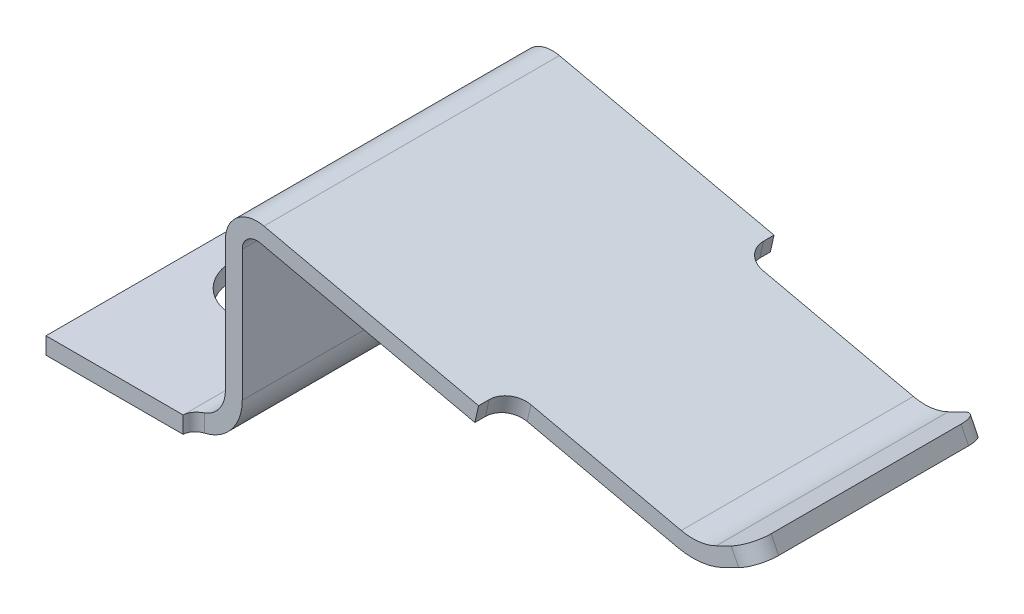
SolidWorks part; units mm, degrees
ref_plane "Спереди" through (0, 0, 0) normal (0, 0, 1) x (1, 0, 0)
ref_plane "Сверху" through (0, 0, 0) normal (0, 1, 0) x (1, 0, 0)
ref_plane "Справа" through (0, 0, 0) normal (1, 0, 0) x (0, 0, -1)
sketch "Эскиз1" plane through (0, 0, 0) normal (0, 0, 1) x (1, 0, 0)
  line L0 (-25.2291, 2.3594) -> (-25.2291, 8.5594)
  line L1 (-33.2291, 0.0594) -> (-26.7291, 0.0594)
  line L2 (-33.2291, 0.0594) -> (-33.2291, 0.8594)
  line L3 (-33.2291, 0.8594) -> (-26.7291, 0.8594)
  line L4 (-24.4291, 2.3594) -> (-24.4291, 8.5594)
  line L5 (-23.4005, 10.023) -> (-5.1266, 5.9201)
  line L6 (-23.5757, 9.2424) -> (-5.3019, 5.1396)
  line L7 (-3.4669, 6.1203) -> (-1.8665, 6.9152)
  line L8 (-3.1111, 5.4038) -> (-1.5106, 6.1987)
  line L9 (-1.8665, 6.9152) -> (-1.5106, 6.1987)
  arc A0 (-5.1266, 5.9201) -> (-3.4669, 6.1203) centre (-4.5789, 8.3594) ccw
  arc A1 (-25.2291, 8.5594) -> (-23.4005, 10.023) centre (-23.7291, 8.5594) cw
  arc A2 (-26.7291, 0.8594) -> (-25.2291, 2.3594) centre (-26.7291, 2.3594) ccw
  arc A3 (-26.7291, 0.0594) -> (-24.4291, 2.3594) centre (-26.7291, 2.3594) ccw
  arc A4 (-24.4291, 8.5594) -> (-23.5757, 9.2424) centre (-23.7291, 8.5594) cw
  arc A5 (-5.3019, 5.1396) -> (-3.1111, 5.4038) centre (-4.5789, 8.3594) ccw
  dimension "D5" = 5
  dimension "D3" = 1.5
  dimension "D9" = 1.5
  dimension "D10" = 18.7288
  dimension "D1" = 0.8
  dimension "D2" = 6.5
  dimension "D4" = 7.5
  dimension "D6" = 3.0683
  dimension "D7" = 18.7288
  dimension "D8" = 8.5
extrude "Вытянуть1" add sketch "Эскиз1" along normal blind 15
sketch "Эскиз2" plane through (0, 0.8594, 0) normal (0, 1, 0) x (1, 0, 0)
  line L0 (-34.6669, -7.5) -> (0, -7.5) construction
  line L1 (-26.7291, -15) -> (-33.2291, -15) construction
  line L2 (-26.7291, 0) -> (-33.2291, 0) construction
  line L3 (-33.2291, -15) -> (-33.2291, 0) construction
  line L4 (-13.2291, -0.5) -> (-13.2291, -2)
  line L5 (-26.7291, 0) -> (-0.7918, 0)
  line L6 (-26.7291, 0) -> (-26.7291, -0.5)
  line L7 (-26.7291, -0.5) -> (-13.2291, -0.5)
  line L8 (-0.7918, 0) -> (-0.7918, -2)
  line L9 (-26.7291, -15) -> (-0.7918, -15)
  line L10 (-26.7291, -15) -> (-26.7291, -14.5)
  line L11 (-26.7291, -14.5) -> (-13.2291, -14.5)
  line L13 (-13.2291, -2) -> (-0.7918, -2)
  line L14 (-0.7918, -15) -> (-0.7918, -13)
  line L15 (-13.2291, -13) -> (-0.7918, -13)
  line L16 (-13.2291, -14.5) -> (-13.2291, -13)
  circle A0 centre (-29.6291, -7.5) radius 2.25
  dimension "D1" = 4.5
  dimension "D2" = 3.6
  dimension "D3" = 20
  dimension "D4" = 5.5
extrude "Вырез-Вытянуть1" cut sketch "Эскиз2" against normal blind 15 and the other way blind 15
sketch "Эскиз3" plane through (0, 0, 14.5) normal (0, 0, 1) x (1, 0, 0)
  line L0 (-13.2291, 7.7393) -> (-13.2291, 6.9194) construction
  line L1 (-13.2291, 7.7393) -> (-13.2291, 6.9194)
  line L2 (-23.5757, 9.2424) -> (-13.2291, 6.9194) construction
  line L3 (-13.4043, 6.9587) -> (-13.2291, 6.9194)
  line L4 (-13.2291, 7.7393) -> (-13.4043, 6.9587)
extrude "Вырез-Вытянуть2" cut sketch "Эскиз3" against normal up to surface (1.5 mm away) up to face at (-5.8502, 6.2531, 13)
sketch "Эскиз4" plane through (0, 0, 0.5) normal (0, 0, -1) x (-1, 0, 0)
  line L0 (13.2291, 7.7393) -> (13.2291, 6.9194) construction
  line L1 (13.2291, 7.7393) -> (13.2291, 6.9194)
  line L2 (13.2291, 6.9194) -> (23.5757, 9.2424) construction
  line L3 (13.2291, 6.9194) -> (13.4043, 6.9587)
  line L4 (13.4043, 6.9587) -> (13.2291, 7.7393) construction
  line L5 (13.4043, 6.9587) -> (13.2291, 7.7393)
extrude "Вырез-Вытянуть3" cut sketch "Эскиз4" against normal up to surface (1.5 mm away) up to face at (-5.8502, 6.2531, 2)
fillet "Скругление1" radius 0.5 2 edges at (-26.7291, 0.4594, 14.5) (-26.7291, 0.4594, 0.5)
fillet "Скругление2" radius 1 4 edges at (-1.6885, 6.5569, 13) (-1.6885, 6.5569, 2) (-13.3167, 7.349, 2) (-13.3167, 7.349, 13)
